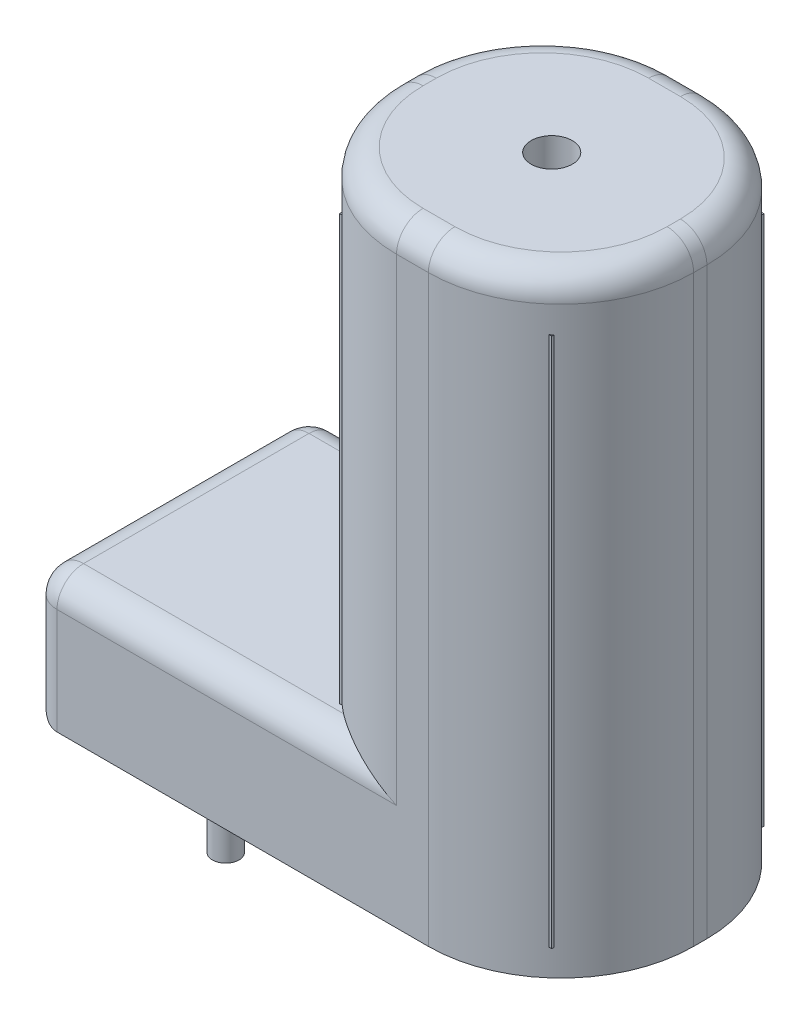
SolidWorks part; units mm, degrees
material "PVB"
ref_plane "Front Plane" through (0, 0, 0) normal (0, 0, 1) x (1, 0, 0)
ref_plane "Top Plane" through (0, 0, 0) normal (0, 1, 0) x (1, 0, 0)
ref_plane "Right Plane" through (0, 0, 0) normal (1, 0, 0) x (0, 0, -1)
sketch "Sketch2" plane through (0, 0, 0) normal (0, 1, 0) x (1, 0, 0)
  line L0 (-100, 0) -> (100, 0) construction
  line L1 (-100, 52.5) -> (100, 52.5)
  line L2 (-100, 52.5) -> (-100, -52.5)
  line L3 (-100, -52.5) -> (100, -52.5)
  line L4 (100, 52.5) -> (100, -52.5)
  line L5 (-100, 52.5) -> (100, -52.5) construction
  line L6 (-100, -52.5) -> (100, 52.5) construction
  circle A1 centre (44, 0) radius 7.75
  point P0 (0, 0)
  dimension "D6" = 15.5
  dimension "D1" = 200
  dimension "D2" = 105
  dimension "D5" = 56
extrude "Boss-Extrude2" add sketch "Sketch2" along normal blind 50
sketch "Sketch3" plane through (0, 0, 0) normal (0, -1, 0) x (1, 0, 0)
  circle A0 centre (-78.8986, 0) radius 15
  dimension "D1" = 30
extrude "Cut-Extrude1" cut sketch "Sketch3" against normal blind 40
sketch "Sketch4" plane through (0, 40, 0) normal (0, -1, 0) x (1, 0, 0)
  circle A0 centre (-78.8986, 0) radius 5
  dimension "D1" = 10
extrude "Boss-Extrude3" add sketch "Sketch4" along normal blind 100
sketch "Sketch5" plane through (0, 50, 0) normal (0, 1, 0) x (1, 0, 0)
  line L1 (-12, 52.5) -> (100, 52.5)
  line L2 (-12, 52.5) -> (-12, -52.5)
  line L3 (-12, -52.5) -> (100, -52.5)
  line L4 (100, 52.5) -> (100, -52.5)
  line L5 (-12, 52.5) -> (100, -52.5) construction
  line L6 (-12, -52.5) -> (100, 52.5) construction
  point P0 (44, 0)
extrude "Boss-Extrude4" add sketch "Sketch5" along normal blind 180
sketch "Sketch7" plane through (0, 50, 0) normal (0, -1, 0) x (1, 0, 0)
  circle A0 centre (44, 0) radius 7.75
extrude "Cut-Extrude2" cut sketch "Sketch7" against normal blind 200
sketch "Sketch8" plane through (0, 50, 0) normal (0, 1, 0) x (1, 0, 0)
  line L1 (4, 40) -> (84, 40)
  line L2 (4, 40) -> (4, -40)
  line L3 (4, -40) -> (84, -40)
  line L4 (84, 40) -> (84, -40)
  line L5 (4, 40) -> (84, -40) construction
  line L6 (4, -40) -> (84, 40) construction
  point P0 (44, 0)
  dimension "D1" = 80
  dimension "D2" = 80
extrude "Cut-Extrude3" cut sketch "Sketch8" along normal blind 160 and the other way blind 40
fillet "Fillet6" radius 10 4 edges at (-100, 50, 0) (-100, 0, 0) (-100, 25, -52.5) (-100, 25, 52.5) type face fillet first side face at (-100, 25, 0) second side face at (-78.8986, 0, -15) second side face at (-4, 93.3333, -52.5) second side face at (-4, 93.3333, 52.5) second side face at (-56, 50, 0)
fillet "Fillet7" radius 10 1 edges at (-51, 50, 52.5) type face fillet first side face at (-51, 50, 0) second side face at (-0.6667, 93.3333, 52.5)
fillet "Fillet8" radius 10 1 edges at (-51, 50, -52.5) type face fillet first side face at (-51, 50, -5) second side face at (-0.6667, 93.3333, -52.5)
fillet "Fillet9" radius 50 1 edges at (100, 115, 52.5) type face fillet first side face at (-0.6667, 90, 52.5) second side face at (100, 115, 0)
fillet "Fillet10" radius 50 1 edges at (-12, 135, 52.5) type face fillet first side face at (-17.3333, 90, 52.5) second side face at (-12, 107.357, 0)
fillet "Fillet11" radius 50 1 edges at (100, 115, -52.5) type face fillet first side face at (-0.6667, 90, -52.5) second side face at (100, 115, -25)
fillet "Fillet12" radius 50 1 edges at (-12, 135, -52.5) type face fillet first side face at (-12, 120.4142, -28.9142) second side face at (-17.3333, 90, -52.5)
fillet "Fillet14" radius 10 4 edges at (100, 230, 0) (44, 230, -52.5) (44, 230, 52.5) (-12, 230, 0) type face fillet first side face at (44, 230, 7.75) second side face at (-12, 140, 0) second side face at (-0.6667, 90, 52.5) second side face at (100, 115, 0) second side face at (-0.6667, 90, -52.5)
